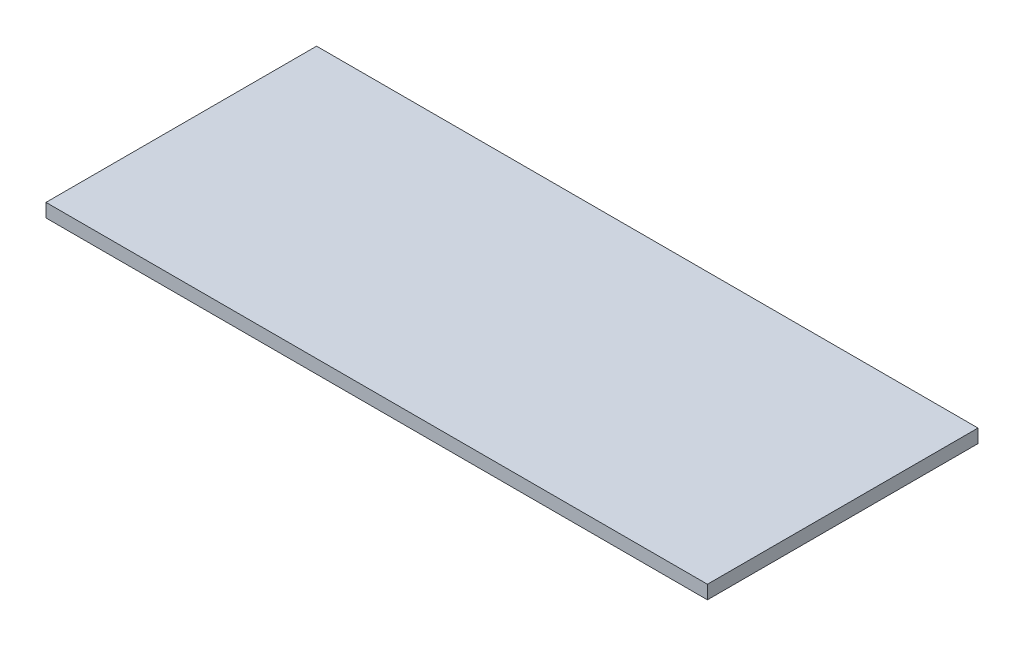
SolidWorks part; units mm, degrees
ref_plane "Front Plane" through (0, 0, 0) normal (0, 0, 1) x (1, 0, 0)
ref_plane "Top Plane" through (0, 0, 0) normal (0, 1, 0) x (1, 0, 0)
ref_plane "Right Plane" through (0, 0, 0) normal (1, 0, 0) x (0, 0, -1)
sketch "Sketch2" plane through (0, 0, 0) normal (0, 1, 0) x (1, 0, 0)
  line L3 (110, 45) -> (-110, 45)
  line L4 (110, 45) -> (110, -45)
  line L5 (110, -45) -> (-110, -45)
  line L6 (-110, 45) -> (-110, -45)
  line L7 (110, 45) -> (-110, -45) construction
  line L8 (110, -45) -> (-110, 45) construction
  point P0 (0, 0)
  dimension "D1" = 220
  dimension "D2" = 90
extrude "Boss-Extrude1" add sketch "Sketch2" along normal blind 4.5
